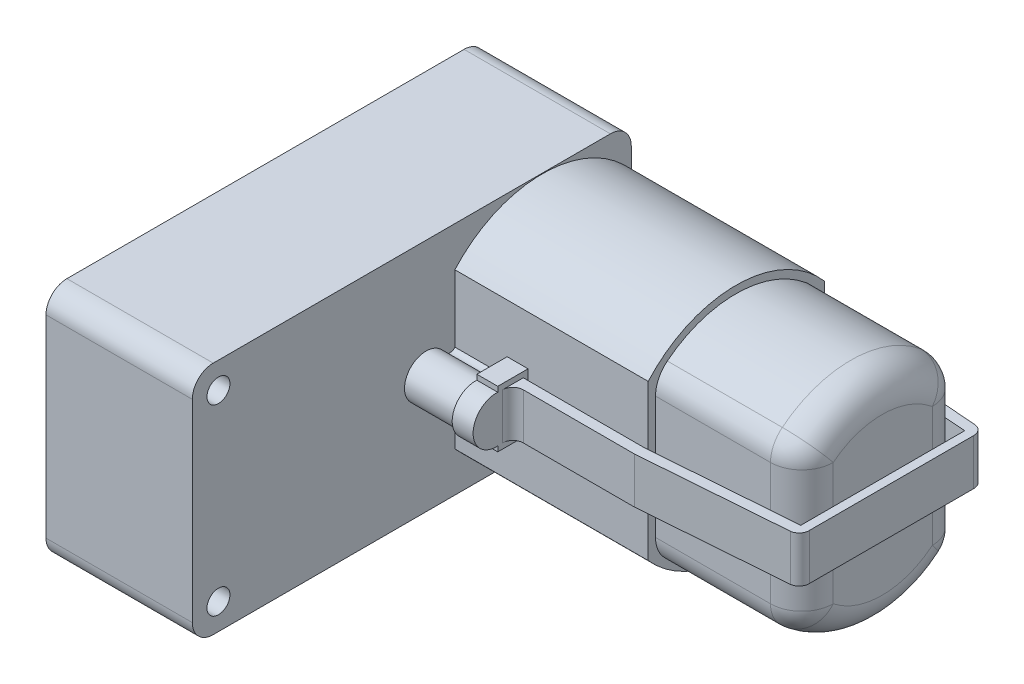
SolidWorks part; units mm, degrees
ref_plane "Front Plane" through (0, 0, 0) normal (0, 0, 1) x (1, 0, 0)
ref_plane "Top Plane" through (0, 0, 0) normal (0, 1, 0) x (1, 0, 0)
ref_plane "Right Plane" through (0, 0, 0) normal (1, 0, 0) x (0, 0, -1)
sketch "Sketch1" plane through (0, 0, 0) normal (0, 1, 0) x (1, 0, 0)
  line L1 (-21.7296, 20.5432) -> (-7.7296, 20.5432)
  line L2 (-21.7296, 20.5432) -> (-21.7296, -21.4568)
  line L3 (-21.7296, -21.4568) -> (-7.7296, -21.4568)
  line L4 (-7.7296, 20.5432) -> (-7.7296, -21.4568)
  dimension "D1" = 42
  dimension "D2" = 14
extrude "Boss-Extrude1" add sketch "Sketch1" along normal blind 22.5
fillet "Fillet1" radius 2 4 edges at (-14.7296, 22.5, -20.5432) (-14.7296, 0, -20.5432) (-14.7296, 0, 21.4568) (-14.7296, 22.5, 21.4568)
sketch "Sketch2" plane through (-7.7296, 0, 0) normal (1, 0, 0) x (0, 0, -1)
  line L0 (-19.4568, 0) -> (18.5432, 0) construction
  line L2 (3.6661, 18.6743) -> (3.6661, 3.8257)
  line L4 (20.5432, 18.5333) -> (20.5432, 3.9667)
  line L5 (20.5432, 20.5) -> (20.5432, 2) construction
  line L6 (-996.4568, 11.25) -> (49003.5432, 11.25) construction
  line L7 (12.0432, -977.25) -> (12.0432, 49022.75) construction
  arc A0 (20.5432, 18.5333) -> (3.6661, 18.6743) centre (12.0432, 11.25) ccw
  arc A1 (3.6661, 3.8257) -> (20.5432, 3.9667) centre (12.0432, 11.25) ccw
  point P11 (3.6661, 11.25)
  dimension "D1" = 11.25
extrude "Boss-Extrude2" add sketch "Sketch2" along normal blind 18.5
sketch "Sketch3" plane through (-7.7296, 0, 0) normal (1, 0, 0) x (0, 0, -1)
  line L0 (3.6661, 11.25) -> (-4.3884, 11.25) construction
  line L1 (3.6661, 18.6743) -> (3.6661, 3.8257) construction
  line L2 (3.6661, 18.6743) -> (3.6661, 3.8257) construction
  line L3 (3.6661, 12.2654) -> (3.6661, 10.3412)
  arc A0 (2.6785, 12.3299) -> (2.7239, 10.2481) centre (0.9148, 11.25) ccw
  arc A1 (2.6785, 12.3299) -> (3.6661, 12.2654) centre (3.1938, 12.6278) ccw
  arc A2 (2.7239, 10.2481) -> (3.6661, 10.3412) centre (3.2261, 9.9798) cw
  dimension "D1" = 2.7513
  dimension "D2" = 2.068
  dimension "D3" = 0.5953
  dimension "D4" = 0.5694
  dimension "D5" = 0.44
  dimension "D6" = 1.2702
  dimension "D7" = 1.3778
  dimension "D8" = 0.4723
extrude "Boss-Extrude3" add sketch "Sketch3" along normal blind 5
sketch "Sketch4" plane through (-7.7296, 0, 0) normal (1, 0, 0) x (0, 0, -1)
  line L0 (-18.9568, -979.1157) -> (-18.9568, 49020.8843) construction
  line L1 (-19.4568, 22.5) -> (18.5432, 22.5) construction
  line L2 (-21.4568, 20.5) -> (-21.4568, 2) construction
  line L3 (-19.4568, 0) -> (18.5432, 0) construction
  circle A0 centre (-18.9568, 20) radius 1.1
  circle A1 centre (-18.9568, 2.5) radius 1.1
  dimension "D1" = 2.5
  dimension "D2" = 2.5
  dimension "D3" = 2.5
extrude "Cut-Extrude1" cut sketch "Sketch4" against normal blind 15
sketch "Sketch5" plane through (0, 0, -20.5432) normal (0, 0, -1) x (-1, 0, 0)
  line L0 (7.7296, 18.5333) -> (7.7296, 3.9667) construction
  line L1 (21.7296, 0) -> (7.7296, 0) construction
  line L2 (6.7296, 9.25) -> (8.7296, 9.25)
  line L3 (6.7296, 9.25) -> (6.7296, 13.25)
  line L4 (6.7296, 13.25) -> (8.7296, 13.25)
  line L5 (8.7296, 9.25) -> (8.7296, 13.25)
  line L6 (6.7296, 9.25) -> (8.7296, 13.25) construction
  line L7 (6.7296, 13.25) -> (8.7296, 9.25) construction
  point P4 (7.7296, 11.25)
  dimension "D1" = 2
  dimension "D2" = 4
extrude "Boss-Extrude4" add sketch "Sketch5" along normal blind 5
sketch "Sketch6" plane through (-6.7296, 0, 0) normal (1, 0, 0) x (0, 0, -1)
  line L0 (25.5432, 13.25) -> (25.5432, 9.25) construction
  line L1 (20.5432, 3.9667) -> (20.5432, 18.5333) construction
  line L2 (20.5432, 13.25) -> (20.5432, 9.25) construction
  line L3 (25.5432, 9.25) -> (20.5432, 9.25) construction
  circle A0 centre (23.5432, 11.25) radius 2
  arc A1 (21.6793, 11.9753) -> (20.5432, 12.2253) centre (21.1327, 12.1978) cw
  arc A2 (21.6793, 10.5247) -> (20.5432, 10.7747) centre (21.0655, 10.4419) ccw
  line M1 (20.5432, 13.25) -> (20.5432, 9.25)
  dimension "D1" = 4
  dimension "D2" = 2
extrude "Boss-Extrude5" add sketch "Sketch6" along normal up to vertex (4 mm away) contours A0 A1 | A2 A0 A1 M1 region at (-6.7296, 11.2501, -23.5435) region at (-6.7296, 11.3517, -21.0299) up to point (-2.7296, 10.2481, -2.7239)
sketch "Sketch7" plane through (-6.7296, 0, 0) normal (1, 0, 0) x (0, 0, -1)
  line L0 (23.5432, 13.25) -> (23.5432, 13.9672)
  line L1 (23.5432, 13.9672) -> (25.7602, 13.9672)
  line L2 (25.7602, 13.9672) -> (25.7602, 8.9705)
  line L3 (25.7602, 8.9705) -> (23.5432, 8.9705)
  line L4 (23.5432, 8.9705) -> (23.5432, 9.25)
  arc A0 (23.5432, 13.25) -> (23.5432, 9.25) centre (23.5432, 11.25) cw
  arc A1 (21.6793, 10.5247) -> (21.6793, 11.9753) centre (23.5432, 11.25) ccw construction
  arc A2 (23.5432, 9.25) -> (25.5432, 11.25) centre (23.5432, 11.25) ccw construction
extrude "Cut-Extrude2" cut sketch "Sketch7" against normal blind 2
sketch "Sketch12" plane through (-21.7296, 0, 0) normal (-1, 0, 0) x (0, 0, 1)
  line L0 (21.4568, 11.25) -> (10.4568, 11.25) construction
  line L1 (21.4568, 20.5) -> (21.4568, 2) construction
  circle A0 centre (10.4568, 11.25) radius 3.5
  circle A1 centre (10.4568, 11.25) radius 3.0703
extrude "Boss-Extrude6" add sketch "Sketch12" along normal blind 1
sketch "Sketch14" plane through (-21.7296, 0, 0) normal (-1, 0, 0) x (0, 0, 1)
  line L0 (-18.5432, 0) -> (19.4568, 0) construction
  line L2 (21.4568, 20.5) -> (21.4568, 2) construction
  circle A0 centre (10.4568, 11.25) radius 3
  dimension "D1" = 6
  dimension "D2" = 11.25
  dimension "D3" = 11
extrude "Boss-Extrude7" add sketch "Sketch14" along normal blind 1
sketch "Sketch15" plane through (-22.7296, 0, 0) normal (-1, 0, 0) x (0, 0, 1)
  line L2 (8.8539, 8.7141) -> (8.8539, 13.7859)
  line L4 (12.0597, 8.7141) -> (12.0597, 13.7859)
  line L5 (8.8539, 8.7141) -> (12.0597, 13.7859) construction
  line L6 (8.8539, 13.7859) -> (12.0597, 8.7141) construction
  circle A0 centre (10.4568, 11.25) radius 3 construction
  circle A1 centre (10.4568, 11.25) radius 1
  arc A2 (8.8539, 8.7141) -> (12.0597, 8.7141) centre (10.4568, 11.25) ccw
  arc A3 (12.0597, 13.7859) -> (8.8539, 13.7859) centre (10.4568, 11.25) ccw
  point P0 (10.4568, 11.25)
  point P1 (10.4568, 11.25)
  dimension "D1" = 6
  dimension "D2" = 2
extrude "Boss-Extrude8" add sketch "Sketch15" along normal blind 7
sketch "Sketch16" plane through (-21.7296, 0, 0) normal (-1, 0, 0) x (0, 0, 1)
  line L0 (21.4568, 11.25) -> (-0.5432, 11.25) construction
  line L1 (21.4568, 20.5) -> (21.4568, 2) construction
  circle A0 centre (-0.5432, 11.25) radius 2
extrude "Boss-Extrude9" add sketch "Sketch16" along normal blind 1.5
sketch "Sketch17" plane through (10.7704, 0, 0) normal (1, 0, 0) x (0, 0, -1)
  line L6 (19.8432, 4.2304) -> (19.8432, 18.2696)
  line L7 (4.3661, 18.4039) -> (4.3661, 4.0961)
  line L8 (19.8432, 4.2304) -> (19.8432, 18.2696)
  line L9 (4.3661, 18.4039) -> (4.3661, 4.0961)
  arc A6 (4.3661, 4.0961) -> (19.8432, 4.2304) centre (12.0432, 11.25) ccw
  arc A7 (19.8432, 18.2696) -> (4.3661, 18.4039) centre (12.0432, 11.25) ccw
  arc A8 (4.3661, 4.0961) -> (19.8432, 4.2304) centre (12.0432, 11.25) ccw
  arc A9 (19.8432, 18.2696) -> (4.3661, 18.4039) centre (12.0432, 11.25) ccw
  dimension "D1" = 0.7
extrude "Cut-Extrude3" cut sketch "Sketch17" against normal up to surface (18.5 mm away) up to face at (-7.7296, 2.5, 17.8568)
sketch "Sketch18" plane through (-7.7296, 0, 0) normal (1, 0, 0) x (0, 0, -1)
  line L2 (19.8432, 4.2304) -> (19.8432, 18.2696)
  line L3 (4.3661, 18.4039) -> (4.3661, 4.0961)
  line L4 (19.8432, 4.2304) -> (19.8432, 18.2696)
  line L5 (4.3661, 18.4039) -> (4.3661, 4.0961)
  arc A2 (4.3661, 4.0961) -> (19.8432, 4.2304) centre (12.0432, 11.25) ccw
  arc A3 (19.8432, 18.2696) -> (4.3661, 18.4039) centre (12.0432, 11.25) ccw
  arc A4 (4.3661, 4.0961) -> (19.8432, 4.2304) centre (12.0432, 11.25) ccw
  arc A5 (19.8432, 18.2696) -> (4.3661, 18.4039) centre (12.0432, 11.25) ccw
  dimension "D1" = 0
extrude "Boss-Extrude10" add sketch "Sketch18" along normal blind 32.5
fillet "Fillet2" radius 3 4 edges at (24.7704, 11.25, -4.3661) (24.7704, 21.7432, -12.1342) (24.7704, 11.25, -19.8432) (24.7704, 0.7568, -12.1342)
fillet "Fillet3" radius 3 8 edges at (16.2704, 18.2696, -19.8432) (16.2704, 4.2304, -19.8432) (16.2704, 4.0961, -4.3661) (16.2704, 18.4039, -4.3661) (23.5476, 18.0422, -19.2601) (23.5476, 4.4578, -19.2601) (23.543, 4.3281, -4.9459) (23.543, 18.1719, -4.9459)
sketch "Sketch19" plane through (-2.7296, 0, 0) normal (1, 0, 0) x (0, 0, -1)
  line L0 (0.768, 13.4734) -> (0.768, 13.9682)
  line L1 (3.6661, 10.3412) -> (3.6661, 12.2654)
  line L3 (3.6661, 8.5318) -> (0.768, 8.5318)
  line L4 (3.6661, 8.5318) -> (3.6661, 13.9682)
  line L5 (3.6661, 13.9682) -> (0.768, 13.9682)
  line L6 (0.768, 8.5318) -> (0.768, 9.0266)
  line L7 (3.6661, 8.5318) -> (0.768, 13.9682) construction
  line L8 (3.6661, 13.9682) -> (0.768, 8.5318) construction
  line L9 (12.1368, 22.4432) -> (12.1368, 0.0568) construction
  line L10 (20.6074, 13.9682) -> (23.5055, 8.5318) construction
  line L11 (20.6074, 8.5318) -> (23.5055, 13.9682) construction
  line L12 (23.5055, 8.5318) -> (23.5055, 9.0266)
  line L13 (20.6074, 13.9682) -> (23.5055, 13.9682)
  line L14 (20.6074, 8.5318) -> (20.6074, 13.9682)
  line L15 (20.6074, 8.5318) -> (23.5055, 8.5318)
  line L16 (23.5055, 13.4734) -> (23.5055, 13.9682)
  line L17 (3.6661, 10.3412) -> (3.6661, 12.2654) construction
  arc A0 (0.768, 13.4734) -> (0.768, 9.0266) centre (0.6367, 11.25) ccw
  arc A1 (20.5432, 18.5333) -> (3.6661, 18.6743) centre (12.0432, 11.25) ccw construction
  arc A2 (3.6661, 3.8257) -> (20.5432, 3.9667) centre (12.0432, 11.25) ccw construction
  arc A3 (21.595, 12.3299) -> (21.5496, 10.2481) centre (23.3587, 11.25) cw construction
  arc A4 (2.6785, 12.3299) -> (3.6661, 12.2654) centre (3.1938, 12.6278) ccw
  arc A5 (2.6785, 12.3299) -> (2.7239, 10.2481) centre (0.9148, 11.25) ccw
  arc A6 (3.6661, 10.3412) -> (2.7239, 10.2481) centre (3.2261, 9.9798) ccw
  arc A8 (2.6785, 12.3299) -> (2.7239, 10.2481) centre (0.9148, 11.25) ccw construction
  arc A9 (23.5055, 13.4734) -> (23.5055, 9.0266) centre (23.6368, 11.25) cw
  point P5 (2.2171, 11.25)
  point P33 (22.0564, 11.25)
  dimension "D1" = 4.4546
  dimension "D4" = 1.5804
  dimension "D5" = 2.8981
  dimension "D6" = 5.4364
  dimension "D2" = 0
extrude "Boss-Extrude11" add sketch "Sketch19" along normal blind 2
ref_plane "Plane1" through (0, 11.25, 0) normal (0, -1, 0) x (-1, 0, 0)
sketch "Sketch22" plane through (0, 11.25, 0) normal (0, -1, 0) x (-1, 0, 0)
  line L0 (0.7296, 3.2085) -> (0.7296, 2.2171)
  line L1 (0.7296, 0.768) -> (0.7296, 3.6661) construction
  line L2 (-10.7704, 3.6661) -> (7.7296, 3.6661) construction
  line L3 (0.7296, 2.2171) -> (-10.9103, 2.2171)
  line L4 (0.7296, 3.2085) -> (-10.9103, 3.2085)
  line L5 (-24.7704, 12.1047) -> (7.7296, 12.1047) construction
  line L6 (-24.7704, 16.8432) -> (-24.7704, 7.3661) construction
  line L7 (7.7296, 20.5432) -> (7.7296, 3.6661) construction
  line L8 (-24.7704, 19.9432) -> (-24.7704, 4.2661)
  line L9 (-24.7704, 16.8432) -> (-24.7704, 7.3661) construction
  line L10 (-24.7704, 4.2661) -> (-10.9103, 3.2085)
  line L11 (-25.6047, 19.9432) -> (-25.6047, 4.2661)
  line L12 (-24.7655, 3.2743) -> (-10.9103, 2.2171)
  line L13 (-24.7655, 20.9351) -> (-10.9103, 21.9923)
  line L14 (-24.7704, 19.9432) -> (-10.9103, 21.0008)
  line L15 (0.7296, 21.0008) -> (-10.9103, 21.0008)
  line L16 (0.7296, 21.9923) -> (-10.9103, 21.9923)
  line L17 (0.7296, 21.0008) -> (0.7296, 21.9923)
  arc A0 (-25.6047, 4.2661) -> (-24.7655, 3.2743) centre (-24.6533, 4.2202) ccw
  arc A1 (-25.6047, 19.9432) -> (-24.7655, 20.9351) centre (-24.6533, 19.9892) cw
  point P25 (-25.6047, 12.1047)
  dimension "D8" = 0.9525
  dimension "D1" = 0.4576
  dimension "D2" = 0.9915
  dimension "D3" = 11.6399
  dimension "D4" = 11.6399
  dimension "D5" = 7.8386
  dimension "D6" = 0.8344
  dimension "D7" = 7.8386
extrude "Boss-Extrude12" add sketch "Sketch22" along normal mid plane 4.4
fillet "Fillet4" radius 1 2 edges at (-0.7296, 11.25, -21.9923) (-0.7296, 11.25, -2.2171)
